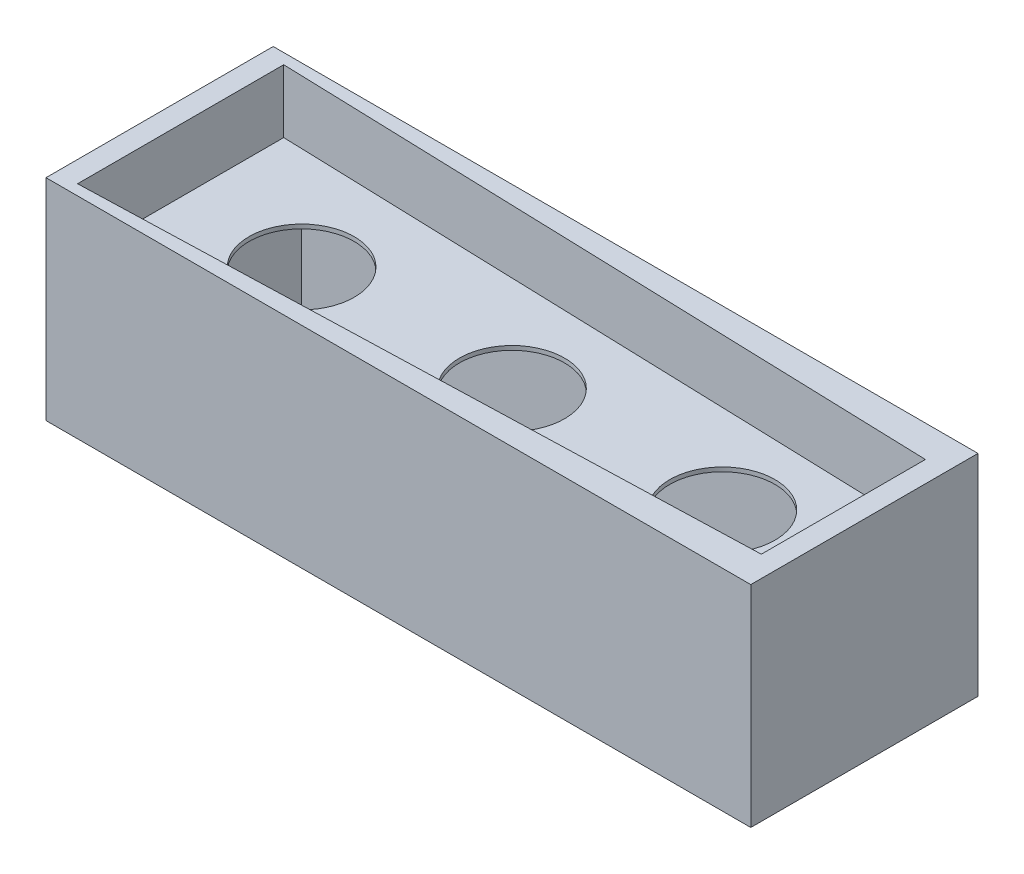
SolidWorks part; units mm, degrees
ref_plane "Front Plane" through (0, 0, 0) normal (0, 0, 1) x (1, 0, 0)
ref_plane "Top Plane" through (0, 0, 0) normal (0, 1, 0) x (1, 0, 0)
ref_plane "Right Plane" through (0, 0, 0) normal (1, 0, 0) x (0, 0, -1)
sketch "Sketch2" plane through (0, 0, 0) normal (0, 1, 0) x (1, 0, 0)
  line L1 (-167.5, 54) -> (167.5, 54)
  line L2 (-167.5, 54) -> (-167.5, -54)
  line L3 (-167.5, -54) -> (167.5, -54)
  line L4 (167.5, 54) -> (167.5, -54)
  line L5 (-167.5, 54) -> (167.5, -54) construction
  line L6 (-167.5, -54) -> (167.5, 54) construction
  point P0 (0, 0)
  dimension "D1" = 335
  dimension "D2" = 108
extrude "Boss-Extrude4" add sketch "Sketch2" against normal blind 100
sketch "Sketch3" plane through (0, 0, 0) normal (0, 1, 0) x (1, 0, 0)
  line L0 (-157.5, -49) -> (-157.5, 49)
  line L1 (157.5, -39) -> (157.5, 39)
  line L2 (-175, 0) -> (175, 0) construction
  line L3 (-157.5, 49) -> (157.5, 39)
  line L4 (157.5, -39) -> (-157.5, -49)
  line L5 (-167.5, 54) -> (-167.5, -54) construction
  line L6 (167.5, -54) -> (167.5, 54) construction
  point P3 (-157.5, 0)
  point P9 (157.5, 0)
  dimension "D1" = 98
  dimension "D2" = 78
  dimension "D3" = 10
  dimension "D4" = 10
  dimension "D5" = 315
extrude "Cut-Extrude1" cut sketch "Sketch3" against normal blind 30 contours L3 L1 L4 L0
sketch "Sketch4" plane through (0, -100, 0) normal (0, -1, 0) x (-1, 0, 0)
  line L1 (150, -50) -> (-150, -50)
  line L2 (150, -50) -> (150, 50)
  line L3 (150, 50) -> (-150, 50)
  line L4 (-150, -50) -> (-150, 50)
  dimension "D1" = 300
  dimension "D2" = 100
extrude "Cut-Extrude2" cut sketch "Sketch4" against normal blind 68 contours L2 L3 L4 L1
sketch "Sketch7" plane through (0, -30, 0) normal (0, 1, 0) x (1, 0, 0)
  circle A0 centre (-100, 0) radius 25
extrude "Cut-Extrude6" cut sketch "Sketch7" against normal blind 61 contours A0
sketch "Sketch8" plane through (0, -30, 0) normal (0, 1, 0) x (1, 0, 0)
  circle A0 centre (0, 0) radius 25
extrude "Cut-Extrude7" cut sketch "Sketch8" against normal blind 61
sketch "Sketch9" plane through (0, -30, 0) normal (0, 1, 0) x (1, 0, 0)
  circle A0 centre (100, 0) radius 25
extrude "Cut-Extrude8" cut sketch "Sketch9" against normal blind 62
